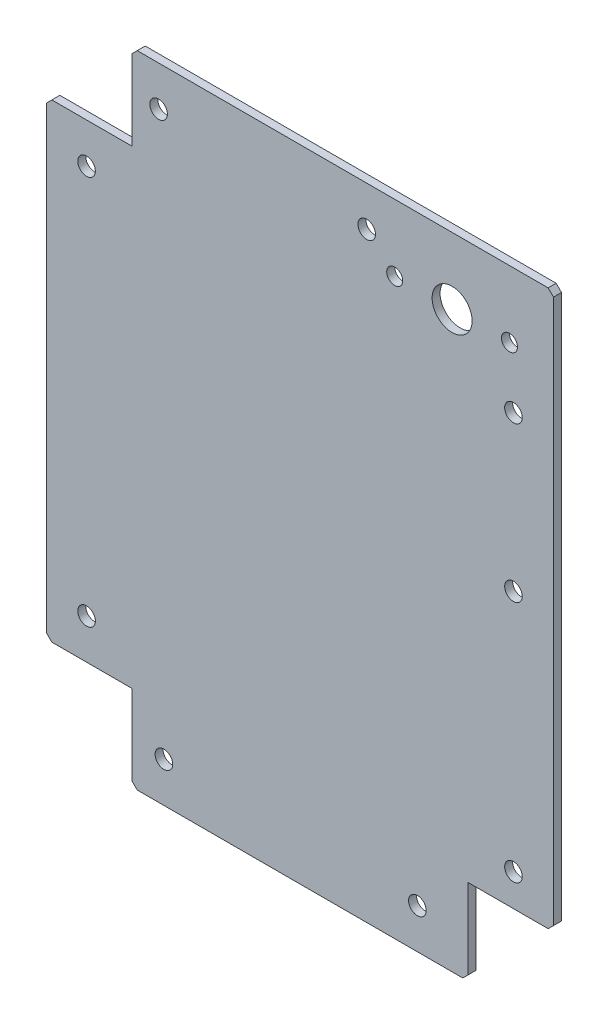
SolidWorks part; units mm, degrees
ref_plane "Front Plane" through (0, 0, 0) normal (0, 0, 1) x (1, 0, 0)
ref_plane "Top Plane" through (0, 0, 0) normal (0, 1, 0) x (1, 0, 0)
ref_plane "Right Plane" through (0, 0, 0) normal (1, 0, 0) x (0, 0, -1)
sketch "Sketch1" plane through (0, 0, 0) normal (0, 0, 1) x (1, 0, 0)
  line L0 (0, 208) -> (32, 208)
  line L1 (32, 0) -> (158, 0)
  line L2 (0, 32) -> (0, 208)
  line L3 (32, 240) -> (190, 240)
  line L4 (190, 32) -> (190, 240)
  line L7 (32, 208) -> (32, 240)
  line L8 (0, 32) -> (32, 32)
  line L9 (32, 32) -> (32, 0)
  line L10 (190, 32) -> (158, 32)
  line L11 (158, 32) -> (158, 0)
  point P0 (0, 0)
  dimension "D1" = 190
  dimension "D2" = 240
  dimension "D3" = 32
  dimension "D4" = 32
  dimension "D5" = 32
  dimension "D6" = 32
  dimension "D7" = 32
  dimension "D8" = 32
  dimension "D9" = 0
  dimension "D10" = 0
base flange "Base-Flange1" sketch "Sketch1" thickness 3 reverse thickness direction no parameters "D1"=0.7366
chamfer "Chamfer1" distance 2 angle 45 7 edges at (0, 208, -1.5) (32, 240, -1.5) (32, 0, -1.5) (0, 32, -1.5) (158, 0, -1.5) (190, 32, -1.5) (190, 240, -1.5)
sketch "Sketch3" plane through (0, 0, 0) normal (0, 0, 1) x (1, 0, 0)
  line L0 (190, 34) -> (190, 238) construction
  line L1 (188, 240) -> (34, 240) construction
  circle A0 centre (130.5, 215) radius 3
  circle A1 centre (173.5, 215) radius 3
  dimension "D1" = 6
  dimension "D2" = 6
  dimension "D3" = 43
  dimension "D4" = 16.5
  dimension "D5" = 25
  dimension "D6" = 25
extrude "Cut-Extrude1" cut sketch "Sketch3" against normal blind 10 normal cut yes
sketch "Sketch4" plane through (0, 0, 0) normal (0, 0, 1) x (1, 0, 0)
  line L1 (188, 240) -> (34, 240) construction
  line L2 (190, 34) -> (190, 238) construction
  line L3 (32, 238) -> (32, 208) construction
  line L4 (34, 0) -> (156, 0) construction
  line L5 (32, 32) -> (32, 2) construction
  line L6 (158, 32) -> (188, 32) construction
  line L7 (0, 206) -> (0, 34) construction
  line L8 (32, 208) -> (2, 208) construction
  line L9 (2, 32) -> (32, 32) construction
  circle A0 centre (42, 225) radius 3.3
  circle A1 centre (120, 225) radius 3.3
  circle A2 centre (175, 193) radius 3.3
  circle A3 centre (175, 135) radius 3.3
  circle A4 centre (175, 44) radius 3.3
  circle A5 centre (139, 15) radius 3.3
  circle A6 centre (44, 15) radius 3.3
  circle A7 centre (15, 193) radius 3.3
  circle A8 centre (15, 47) radius 3.3
  circle A9 centre (152, 215) radius 7.5
  circle A10 centre (173.5, 215) radius 3 construction
  dimension "D1" = 6.6
  dimension "D2" = 6.6
  dimension "D4" = 6.6
  dimension "D5" = 6.6
  dimension "D6" = 6.6
  dimension "D7" = 6.6
  dimension "D8" = 6.6
  dimension "D9" = 6.6
  dimension "D10" = 15
  dimension "D11" = 21.5
  dimension "D12" = 25
  dimension "D13" = 15
  dimension "D14" = 6.6
  dimension "D16" = 15
  dimension "D17" = 10
  dimension "D18" = 70
  dimension "D19" = 15
  dimension "D20" = 15
  dimension "D21" = 12
  dimension "D22" = 95
  dimension "D23" = 15
  dimension "D24" = 135
  dimension "D25" = 15
  dimension "D26" = 12
  dimension "D27" = 15
  dimension "D28" = 15
  dimension "D29" = 15
  dimension "D30" = 15
extrude "Cut-Extrude2" cut sketch "Sketch4" against normal blind 10 normal cut yes
sketch "Bend-Lines1" [suppressed] plane through (0, 0, 0) normal (0, 1, 0) x (1, 0, 0)
sketch "Bounding-Box1" [suppressed] plane through (0, 0, 0) normal (0, 1, 0) x (1, 0, 0)
sheet metal parameters "Sheet-Metal1" thickness 3 parameters "D1"=0.7366
flat pattern "Flat-Pattern1" [suppressed]
sketch "Bend-Lines2" plane through (0, 0, 0) normal (0, 1, 0) x (1, 0, 0)
sketch3d "Bounding-Box2" [suppressed]
  line L0 (200, 240, 0) -> (200, 0, 0) construction
  line L1 (0, 240, 0) -> (0, 0, 0) construction
  line L2 (200, 240, 0) -> (0, 240, 0) construction
  line L3 (200, 0, 0) -> (0, 0, 0) construction
sheet metal parameters "Sheet-Metal2" thickness 3 parameters "D1"=0.7366
flat pattern "Flat-Pattern1"
sketch "Bend-Lines2" plane through (0, 0, 0) normal (0, 1, 0) x (1, 0, 0)
sketch3d "Bounding-Box2" [suppressed]
  line L0 (190, 240, 0) -> (190, 0, 0) construction
  line L1 (0, 240, 0) -> (0, 0, 0) construction
  line L2 (190, 240, 0) -> (0, 240, 0) construction
  line L3 (190, 0, 0) -> (0, 0, 0) construction
sheet metal parameters "Sheet-Metal3" thickness 3 parameters "D1"=0.7366
flat pattern "Flat-Pattern1"
sketch "Bend-Lines2" plane through (0, 0, 0) normal (0, 1, 0) x (1, 0, 0)
sketch3d "Bounding-Box2" [suppressed]
  line L0 (190, 240, 0) -> (190, 0, 0) construction
  line L1 (0, 240, 0) -> (0, 0, 0) construction
  line L2 (190, 240, 0) -> (0, 240, 0) construction
  line L3 (190, 0, 0) -> (0, 0, 0) construction
